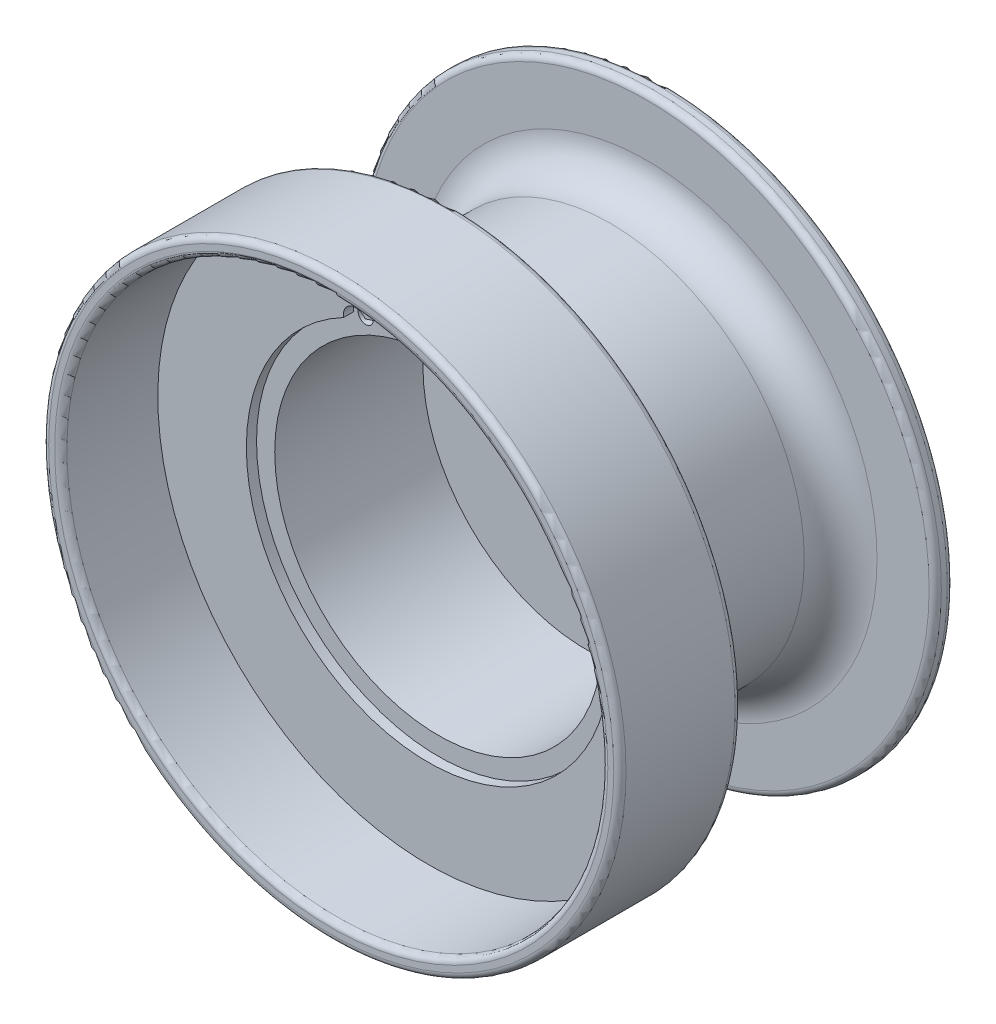
SolidWorks part; units mm, degrees
note: '?' marks a value the reader was unsure of.
ref_plane "Front" through (0, 0, 0) normal (0, 0, 1) x (1, 0, 0)
ref_plane "Top" through (0, 0, 0) normal (0, 1, 0) x (1, 0, 0)
ref_plane "Right" through (0, 0, 0) normal (1, 0, 0) x (0, 0, -1)
sketch "Sketch1" plane through (0, 0, 0) normal (-1, 0, 0) x (0, 0, 1)
  line L0 (-101.8682, 0) -> (101.5211, 0) construction
  line L1 (0, 31.369) -> (0, 75.565)
  line L2 (0, 75.565) -> (4.7625, 75.565)
  line L3 (4.7625, 75.565) -> (4.7625, 60.325)
  line L4 (14.2875, 50.8) -> (46.0375, 50.8)
  line L5 (55.5625, 60.325) -> (55.5625, 75.565)
  line L6 (55.5625, 75.565) -> (87.3125, 75.565)
  line L7 (87.3125, 75.565) -> (87.3125, 70.8025)
  line L8 (87.3125, 70.8025) -> (61.9125, 70.8025)
  line L9 (61.9125, 70.8025) -> (61.9125, 47.625)
  line L10 (59.2455, 42.8625) -> (20.447, 42.8625)
  line L11 (20.447, 42.8625) -> (20.447, 6.35)
  line L13 (61.9125, 47.625) -> (59.2455, 47.625)
  line L14 (59.2455, 47.625) -> (59.2455, 42.8625)
  line L15 (0, 31.369) -> (9.525, 31.369)
  line L16 (9.525, 31.369) -> (9.525, 6.35)
  line L17 (9.525, 6.35) -> (20.447, 6.35)
  arc A0 (4.7625, 60.325) -> (14.2875, 50.8) centre (14.2875, 60.325) ccw
  arc A1 (46.0375, 50.8) -> (55.5625, 60.325) centre (46.0375, 60.325) ccw
  dimension "D17" = 9.525
  dimension "D1" = 50.8
  dimension "D2" = 4.7625
  dimension "D3" = 6.35
  dimension "D4" = 25.4
  dimension "D5" = 101.6
  dimension "D6" = 7.9375
  dimension "D7" = 151.13
  dimension "D8" = 9.525
  dimension "D9" = 2.667
  dimension "D10" = 95.25
  dimension "D11" = 62.738
  dimension "D12" = 12.7
  dimension "D13" = 20.447
  dimension "D16" = 10.922
  dimension "D19" = 85.725
  dimension "D20" = 141.605
revolve "Base-Revolve" add sketch "Sketch1" angle 360 about L0
ref_axis "Axis1" through (0, 0, 146.8843) along (0, 0, -1)?
sketch "Sketch6" plane through (0, 0, 61.9125) normal (0, 0, 1) x (1, 0, 0)
  circle A0 centre (0, 62.865) radius 6.35
  circle A3 centre (0, 0) radius 70.8025 construction
  dimension "D1" = 12.7
  dimension "D2" = 1.5875
extrude "Cut-Extrude5" cut sketch "Sketch6" against normal up to next
fillet "Fillet2" radius 1.5875
sketch "Sketch8" plane through (0, 0, 61.9125) normal (0, 0, 1) x (1, 0, 0)
  line L1 (0, -50) -> (0, 50) construction
  circle A0 centre (19.05, 42.7816) radius 1.9844
  circle A1 centre (-19.05, 42.7816) radius 1.9844
  circle A3 centre (0, 0) radius 46.8312 construction
  dimension "D1" = 3.9688
  dimension "D3" = 19.05
  dimension "D4" = 38.1
  dimension "D2" = 93.6625
extrude "Cut-Extrude6" cut sketch "Sketch8" against normal blind 12.7
fillet "Fillet3" radius 1.6002
sketch "Sketch9" plane through (0, 0, 59.2455) normal (0, 0, 1) x (1, 0, 0)
  circle A0 centre (19.05, 42.7816) radius 3.175
  circle A1 centre (-19.05, 42.7816) radius 3.175
  dimension "D1" = 6.35
extrude "Cut-Extrude7" cut sketch "Sketch9" along normal through all
sketch "Sketch10" plane through (0, 0, 9.525) normal (0, 0, -1) x (-1, 0, 0)
  circle A0 centre (-25.4, 0) radius 3.3734
  circle A1 centre (0, 0) radius 25.4 construction
  dimension "D1" = 50.8
  dimension "D2" = 6.7469
extrude "Cut-Extrude8" cut sketch "Sketch10" against normal through all
